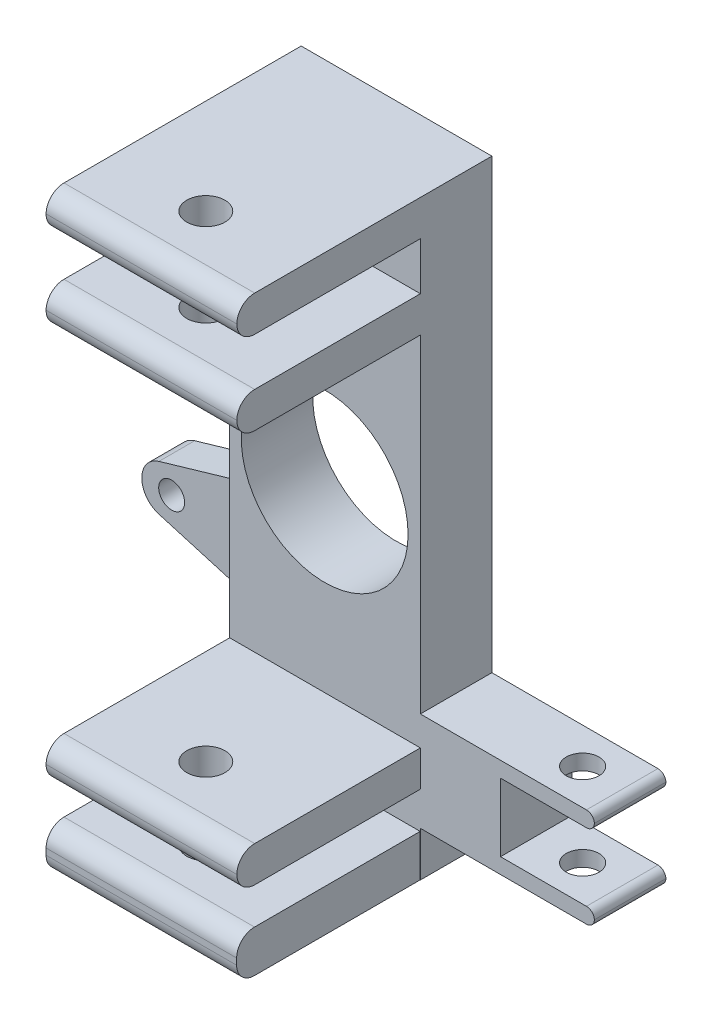
SolidWorks part; units mm, degrees
ref_plane "Front Plane" through (0, 0, 0) normal (0, 0, 1) x (1, 0, 0)
ref_plane "Top Plane" through (0, 0, 0) normal (0, 1, 0) x (1, 0, 0)
ref_plane "Right Plane" through (0, 0, 0) normal (1, 0, 0) x (0, 0, -1)
sketch "Sketch2" plane through (0, 0, 0) normal (0, 0, 1) x (1, 0, 0)
  line L0 (80, 60.32) -> (153, 60.32)
  line L1 (0, 0) -> (80, 0)
  line L2 (0, 0) -> (0, 248)
  line L3 (0, 248) -> (80, 248)
  line L4 (80, 0) -> (80, 248)
  line L5 (153, 60.32) -> (153, 53.83)
  line L6 (153, 53.83) -> (113.63, 53.83)
  line L7 (113.63, 53.83) -> (113.63, 25.2846)
  line L8 (113.63, 25.2846) -> (153, 25.2846)
  line L9 (153, 25.2846) -> (153, 18.7946)
  line L10 (153, 18.7946) -> (80, 18.7946)
  line L11 (0, 72.66) -> (-160.553, 72.66) construction
  line L12 (0, 95.32) -> (-44.6724, 82.2581)
  line L13 (0, 50) -> (-44.6724, 63.0619)
  line L14 (0, 13.04) -> (-65.9163, 13.04) construction
  line L15 (-10.5315, 3.3143) -> (0, 0.7954)
  line L16 (-10.5315, 22.7657) -> (0, 25.2846)
  arc A0 (-44.6724, 82.2581) -> (-44.6724, 63.0619) centre (-41.866, 72.66) ccw
  arc A1 (-10.5315, 3.3143) -> (-10.5315, 22.7657) centre (-8.2053, 13.04) cw
  point P20 (-77.4986, 72.66)
  point P21 (-51.866, 72.66)
  point P29 (-51.1942, 13.04)
  point P30 (-18.2053, 13.04)
  dimension "D10" = 10
  dimension "D12" = 10
  dimension "D1" = 248
  dimension "D2" = 80
  dimension "D3" = 187.68
  dimension "D4" = 73
  dimension "D5" = 6.49
  dimension "D6" = 39.37
  dimension "D7" = 175.34
  dimension "D8" = 22.66
  dimension "D9" = 56.6
  dimension "D11" = 13.04
  dimension "D13" = 21.94
extrude "Boss-Extrude1" add sketch "Sketch2" along normal blind 30 contours L1 L4 L3 L2 | L10 L9 L8 L7 L6 L5 L0 L4 region at (106.5933, 39.5573, 0) region at (40, 124, 0)
extrude "Boss-Extrude2" add sketch "Sketch2<5>" along normal blind 15 contours L12 A0 L13 L2 | A1 L15 L2 L16 region at (-21.1897, 72.66, 0) region at (-7.874, 13.04, 0)
sketch "Sketch2<5>" plane through (0, 0, 0) normal (0, 0, 1) x (1, 0, 0) same geometry as "Sketch2"
sketch "Sketch3" plane through (0, 0, 0) normal (0, 0, 1) x (1, 0, 0)
  line L0 (80, 60.32) -> (80, 248) construction
  line L1 (0, 248) -> (80, 248)
  line L2 (0, 248) -> (0, 233)
  line L3 (0, 233) -> (80, 233)
  line L4 (80, 248) -> (80, 233)
  line L5 (0, 0) -> (0, 248) construction
  line L6 (0, 213) -> (80, 213)
  line L7 (0, 213) -> (0, 198)
  line L8 (0, 198) -> (80, 198)
  line L9 (80, 213) -> (80, 198)
  line L11 (0, 33) -> (80, 33)
  line L12 (0, 33) -> (0, 48)
  line L13 (0, 48) -> (80, 48)
  line L14 (80, 33) -> (80, 48)
  line L15 (0, 0) -> (79.928, 0)
  line L16 (0, 0) -> (0, 17.63)
  line L17 (0, 17.63) -> (79.928, 17.63)
  line L18 (79.928, 0) -> (79.928, 17.63)
  dimension "D1" = 15
  dimension "D2" = 15
  dimension "D3" = 20
  dimension "D4" = 150
  dimension "D5" = 15
  dimension "D6" = 17.63
extrude "Boss-Extrude3" add sketch "Sketch3" along normal blind 107
fillet "Fillet1" radius 7.5 8 edges at (39.964, 0, 107) (39.964, 17.63, 107) (40, 33, 107) (40, 48, 107) (40, 198, 107) (40, 213, 107) (40, 233, 107) (40, 248, 107)
fillet "Fillet2" radius 3.33 4 edges at (153, 18.7946, 15) (153, 25.2846, 15) (153, 53.83, 15) (153, 60.32, 15)
sketch "Sketch4" plane through (0, 0, 0) normal (0, 0, 1) x (1, 0, 0)
  line L0 (-0.1514, 123) -> (79.8486, 123) construction
  circle A0 centre (39.8486, 123) radius 35
  point P2 (39.8486, 123)
  dimension "D3" = 70
  dimension "D1" = 40
  dimension "D2" = 125
extrude "Cut-Extrude1" cut sketch "Sketch4" against normal through all and the other way through all
sketch "Sketch5" plane through (0, 0, 0) normal (0, 1, 0) x (1, 0, 0)
  line L0 (0, -80) -> (80, -80) construction
  line L1 (0, -99.5) -> (0, 0) construction
  line L2 (80, -99.5) -> (80, 0) construction
  line L3 (0, 0) -> (80, 0) construction
  circle A0 centre (40, -80) radius 8
  dimension "D2" = 16
  dimension "D1" = 80
extrude "Cut-Extrude2" cut sketch "Sketch5" against normal through all and the other way through all
sketch "Sketch6" plane through (0, 60.32, 0) normal (0, 1, 0) x (1, 0, 0)
  line L0 (133.07, 0) -> (133.07, -30) construction
  line L1 (80, 0) -> (149.67, 0) construction
  line L2 (80, -30) -> (149.67, -30) construction
  circle A0 centre (133.07, -15) radius 6.8559
  dimension "D1" = 53.07
extrude "Cut-Extrude3" cut sketch "Sketch6" against normal through all
sketch "Sketch7" plane through (0, 0, 15) normal (0, 0, 1) x (1, 0, 0)
  line L0 (-51.866, 72.66) -> (0, 72.66) construction
  line L1 (0, 50) -> (0, 95.32) construction
  arc A0 (-44.6724, 82.2581) -> (-44.6724, 63.0619) centre (-41.866, 72.66) ccw construction
  circle A1 centre (-39.33, 72.66) radius 5.4415
  dimension "D1" = 39.33
extrude "Cut-Extrude4" cut sketch "Sketch7" against normal through all
sketch "Sketch8" plane through (0, 0, 15) normal (0, 0, 1) x (1, 0, 0)
  line L0 (-18.2053, 13.04) -> (0, 13.04) construction
  line L1 (0, 0.7954) -> (0, 25.2846) construction
  arc A0 (-10.5315, 22.7657) -> (-10.5315, 3.3143) centre (-8.2053, 13.04) ccw construction
  circle A1 centre (-7.83, 13.04) radius 4
  dimension "D2" = 8
  dimension "D1" = 7.83
extrude "Cut-Extrude5" cut sketch "Sketch8" against normal through all
